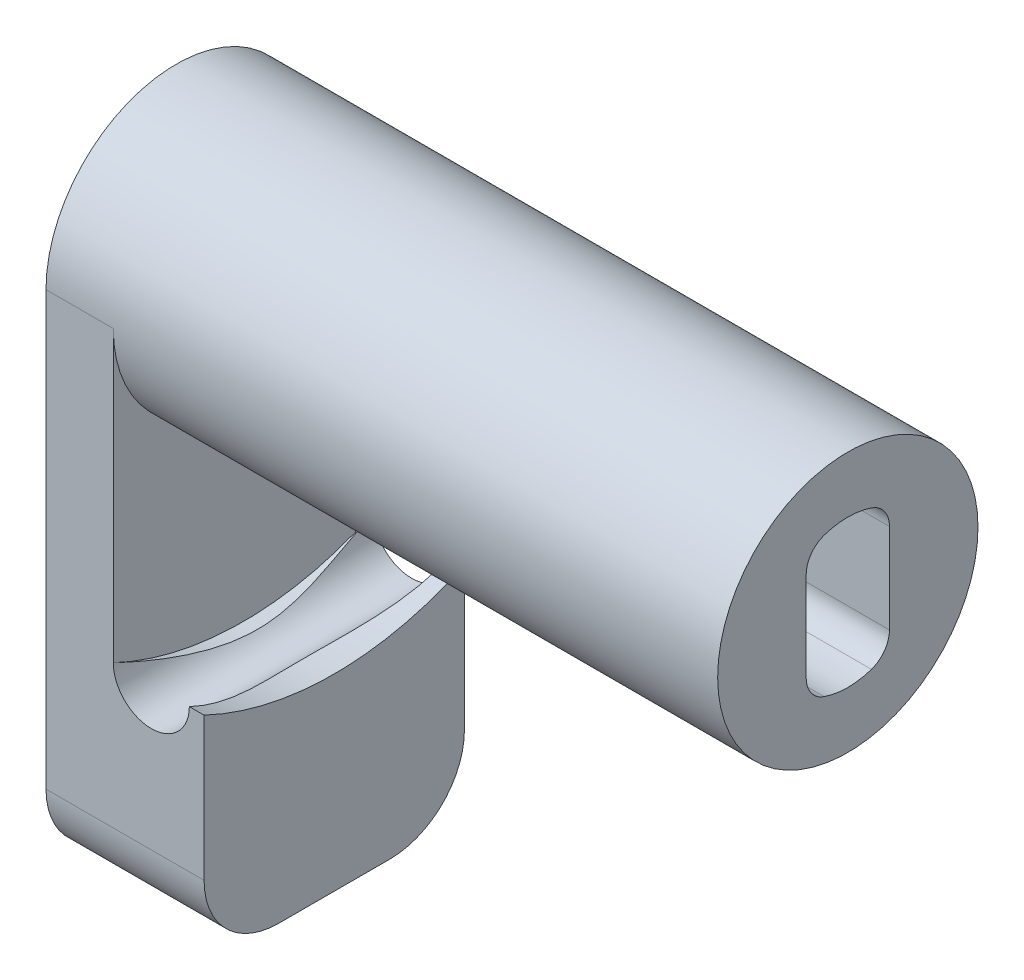
SolidWorks part; units mm, degrees
material "ABS"
ref_plane "Front Plane" through (0, 0, 0) normal (1, 0, 0) x (0, 1, 0)
ref_plane "Top Plane" through (0, 0, 0) normal (0, 0, 1) x (0, 1, 0)
ref_plane "Right Plane" through (0, 0, 0) normal (0, 1, 0) x (-1, 0, 0)
sketch "Sketch1" plane through (0, 0, 0) normal (1, 0, 0) x (0, 1, 0)
  circle A2 centre (0, 0) radius 8.7376
  dimension "D3" = 17.4752
extrude "Boss-Extrude1" add sketch "Sketch1" along normal blind 45.085 contours A2 region at (0, 0, 0)
sketch "Sketch10" plane through (0, 0, 0) normal (-1, 0, 0) x (0, -1, 0)
  line L0 (0, 8.7376) -> (34.036, 8.7376)
  line L2 (34.036, 8.7376) -> (34.036, -8.7376)
  line L3 (34.036, -8.7376) -> (0, -8.7376)
  circle A0 centre (0, 0) radius 8.7376 construction
  arc A2 (0, 8.7376) -> (0, -8.7376) centre (0, 0) cw
  dimension "D1" = 34.036
extrude "Boss-Extrude3" add sketch "Sketch10" against normal blind 4.516 contours L0 A2 L3 L2 region at (0, -20.3793, 0)
fillet "Fillet2" radius 5 2 edges at (2.258, -34.036, 8.7376) (2.258, -34.036, -8.7376)
sketch "Sketch14" [suppressed] plane through (0, 0, 0) normal (-1, 0, 0) x (0, 0, 1)
  line L0 (0.5115, -3.4237) -> (0.3944, -4.0089)
  line L1 (0, 0) -> (0, -4.064) construction
  line L2 (0, 0) -> (0.5606, -3.4335) construction
  line L3 (0.6039, -3.4087) -> (0.9011, -3.9262)
  line L4 (-0.6903, -3.3922) -> (-1.0005, -3.9021)
  line L5 (-0.5983, -3.4096) -> (-0.4961, -3.9976)
  line L6 (-1.8089, -2.9515) -> (-2.2748, -3.3245)
  line L7 (-1.7284, -2.9994) -> (-1.8334, -3.5869)
  line L8 (-2.7093, -2.1549) -> (-3.2746, -2.346)
  line L9 (-2.65, -2.2273) -> (-2.9496, -2.7435)
  line L10 (-3.2829, -1.0983) -> (-3.8795, -1.0846)
  line L11 (-3.252, -1.1867) -> (-3.7101, -1.5692)
  line L12 (-3.4605, 0.0907) -> (-4.0165, 0.3077)
  line L13 (-3.4617, -0.0029) -> (-4.023, -0.2057)
  line L14 (-3.2208, 1.2689) -> (-3.669, 1.6629)
  line L15 (-3.2539, 1.1813) -> (-3.8507, 1.1827)
  line L16 (-2.5926, 2.2939) -> (-2.879, 2.8175)
  line L17 (-2.6537, 2.223) -> (-3.214, 2.4284)
  line L18 (-1.6517, 3.0423) -> (-1.7417, 3.6323)
  line L19 (-1.7333, 2.9965) -> (-2.1896, 3.3812)
  line L20 (-0.5115, 3.4237) -> (-0.3944, 4.0089)
  line L21 (-0.6039, 3.4087) -> (-0.9011, 3.9262)
  line L22 (0.6903, 3.3922) -> (1.0005, 3.9021)
  line L23 (0.5983, 3.4096) -> (0.4961, 3.9976)
  line L24 (1.8089, 2.9515) -> (2.2748, 3.3245)
  line L25 (1.7284, 2.9994) -> (1.8334, 3.5869)
  line L26 (2.7093, 2.1549) -> (3.2746, 2.346)
  line L27 (2.65, 2.2273) -> (2.9496, 2.7435)
  line L28 (3.2829, 1.0983) -> (3.8795, 1.0846)
  line L29 (3.252, 1.1867) -> (3.7101, 1.5692)
  line L30 (3.4605, -0.0907) -> (4.0165, -0.3077)
  line L31 (3.4617, 0.0029) -> (4.023, 0.2057)
  line L32 (3.2208, -1.2689) -> (3.669, -1.6629)
  line L33 (3.2539, -1.1813) -> (3.8507, -1.1827)
  line L34 (2.5926, -2.2939) -> (2.879, -2.8175)
  line L35 (2.6537, -2.223) -> (3.214, -2.4284)
  line L36 (1.6517, -3.0423) -> (1.7417, -3.6323)
  line L37 (1.7333, -2.9965) -> (2.1896, -3.3812)
  line L38 (-0.1032, -4.0627) -> (0, -4.064)
  line L39 (-1.4865, -3.7824) -> (-1.39, -3.8189)
  line L40 (-2.6905, -3.0459) -> (-2.6123, -3.1132)
  line L41 (-3.5195, -2.032) -> (-3.57, -1.942)
  line L42 (-4.0023, -0.7057) -> (-4.0189, -0.6039)
  line L43 (-4.0023, 0.7057) -> (-3.9831, 0.8071)
  line L44 (-3.5195, 2.032) -> (-3.4668, 2.1207)
  line L45 (-2.6123, 3.1132) -> (-2.5324, 3.1785)
  line L46 (-1.39, 3.8189) -> (-1.2926, 3.853)
  line L47 (0, 4.064) -> (0.1032, 4.0627)
  line L48 (1.39, 3.8189) -> (1.4865, 3.7824)
  line L49 (2.6123, 3.1132) -> (2.6905, 3.0459)
  line L50 (3.5195, 2.032) -> (3.57, 1.942)
  line L51 (4.0023, 0.7057) -> (4.0189, 0.6039)
  line L52 (4.0023, -0.7057) -> (3.9831, -0.8071)
  line L53 (3.5195, -2.032) -> (3.4668, -2.1207)
  line L54 (2.6123, -3.1132) -> (2.5324, -3.1785)
  line L55 (1.39, -3.8189) -> (1.2926, -3.853)
  arc A0 (0.3497, -4.0489) -> (0, -4.064) centre (0, 0) cw
  arc A1 (0.3497, -4.0489) -> (0.3944, -4.0089) centre (0.3454, -3.9991) ccw
  arc A2 (0.5115, -3.4237) -> (0.6039, -3.4087) centre (0.5606, -3.4335) cw
  arc A3 (0.4203, -4.0631) -> (0.3944, -4.0089) centre (0.4434, -4.0187) cw
  arc A4 (0.4203, -4.0631) -> (0.7372, -4.2116) centre (2.3016, -0.4608) ccw
  arc A6 (0.9562, -3.9499) -> (0.9011, -3.9262) centre (0.9445, -3.9013) cw
  arc A7 (0.9562, -3.9499) -> (1.2926, -3.853) centre (0, 0) ccw
  arc A8 (-1.0562, -3.9243) -> (-1.39, -3.8189) centre (0, 0) cw
  arc A9 (-1.0562, -3.9243) -> (-1.0005, -3.9021) centre (-1.0432, -3.8761) ccw
  arc A10 (-0.6903, -3.3922) -> (-0.5983, -3.4096) centre (-0.6476, -3.4182) cw
  arc A11 (-0.4524, -4.0387) -> (-0.4961, -3.9976) centre (-0.4468, -3.9891) cw
  arc A12 (-0.4524, -4.0387) -> (-0.1032, -4.0627) centre (0, 0) ccw
  arc A13 (-2.3347, -3.3264) -> (-2.6123, -3.1132) centre (0, 0) cw
  arc A14 (-2.3347, -3.3264) -> (-2.2748, -3.3245) centre (-2.306, -3.2855) ccw
  arc A15 (-1.8089, -2.9515) -> (-1.7284, -2.9994) centre (-1.7776, -2.9906) cw
  arc A16 (-1.8064, -3.6405) -> (-1.8334, -3.5869) centre (-1.7842, -3.5957) cw
  arc A17 (-1.8064, -3.6405) -> (-1.4865, -3.7824) centre (0, 0) ccw
  arc A18 (-3.3316, -2.3273) -> (-3.5195, -2.032) centre (0, 0) cw
  arc A19 (-3.3316, -2.3273) -> (-3.2746, -2.346) centre (-3.2906, -2.2987) ccw
  arc A20 (-2.7093, -2.1549) -> (-2.65, -2.2273) centre (-2.6933, -2.2022) cw
  arc A21 (-2.9426, -2.8031) -> (-2.9496, -2.7435) centre (-2.9064, -2.7686) cw
  arc A22 (-2.9426, -2.8031) -> (-2.6905, -3.0459) centre (0, 0) ccw
  arc A23 (-3.9267, -1.0475) -> (-4.0023, -0.7057) centre (0, 0) cw
  arc A24 (-3.9267, -1.0475) -> (-3.8795, -1.0846) centre (-3.8784, -1.0346) ccw
  arc A25 (-3.2829, -1.0983) -> (-3.252, -1.1867) centre (-3.284, -1.1483) cw
  arc A26 (-3.7238, -1.6276) -> (-3.7101, -1.5692) centre (-3.678, -1.6076) cw
  arc A27 (-3.7238, -1.6276) -> (-3.57, -1.942) centre (0, 0) ccw
  arc A28 (-4.0481, 0.3587) -> (-4.0023, 0.7057) centre (0, 0) cw
  arc A29 (-4.0481, 0.3587) -> (-4.0165, 0.3077) centre (-3.9983, 0.3543) ccw
  arc A30 (-3.4605, 0.0907) -> (-3.4617, -0.0029) centre (-3.4787, 0.0442) cw
  arc A31 (-4.0559, -0.2558) -> (-4.023, -0.2057) centre (-4.006, -0.2527) cw
  arc A32 (-4.0559, -0.2558) -> (-4.0189, -0.6039) centre (0, 0) ccw
  arc A33 (-3.6813, 1.7216) -> (-3.5195, 2.032) centre (0, 0) cw
  arc A34 (-3.6813, 1.7216) -> (-3.669, 1.6629) centre (-3.636, 1.7005) ccw
  arc A35 (-3.2208, 1.2689) -> (-3.2539, 1.1813) centre (-3.2538, 1.2313) cw
  arc A36 (-3.8988, 1.1468) -> (-3.8507, 1.1827) centre (-3.8509, 1.1327) cw
  arc A37 (-3.8988, 1.1468) -> (-3.9831, 0.8071) centre (0, 0) ccw
  arc A38 (-2.8705, 2.8769) -> (-2.6123, 3.1132) centre (0, 0) cw
  arc A39 (-2.8705, 2.8769) -> (-2.879, 2.8175) centre (-2.8352, 2.8415) ccw
  arc A40 (-2.5926, 2.2939) -> (-2.6537, 2.223) centre (-2.6365, 2.2699) cw
  arc A41 (-3.2715, 2.4111) -> (-3.214, 2.4284) centre (-3.2312, 2.3815) cw
  arc A42 (-3.2715, 2.4111) -> (-3.4668, 2.1207) centre (0, 0) ccw
  arc A43 (-1.7134, 3.6852) -> (-1.39, 3.8189) centre (0, 0) cw
  arc A44 (-1.7134, 3.6852) -> (-1.7417, 3.6323) centre (-1.6923, 3.6398) ccw
  arc A45 (-1.6517, 3.0423) -> (-1.7333, 2.9965) centre (-1.7011, 3.0348) cw
  arc A46 (-2.2495, 3.3846) -> (-2.1896, 3.3812) centre (-2.2218, 3.343) cw
  arc A47 (-2.2495, 3.3846) -> (-2.5324, 3.1785) centre (0, 0) ccw
  arc A48 (-0.3497, 4.0489) -> (0, 4.064) centre (0, 0) cw
  arc A49 (-0.3497, 4.0489) -> (-0.3944, 4.0089) centre (-0.3454, 3.9991) ccw
  arc A50 (-0.5115, 3.4237) -> (-0.6039, 3.4087) centre (-0.5606, 3.4335) cw
  arc A51 (-0.9562, 3.9499) -> (-0.9011, 3.9262) centre (-0.9445, 3.9013) cw
  arc A52 (-0.9562, 3.9499) -> (-1.2926, 3.853) centre (0, 0) ccw
  arc A53 (1.0562, 3.9243) -> (1.39, 3.8189) centre (0, 0) cw
  arc A54 (1.0562, 3.9243) -> (1.0005, 3.9021) centre (1.0432, 3.8761) ccw
  arc A55 (0.6903, 3.3922) -> (0.5983, 3.4096) centre (0.6476, 3.4182) cw
  arc A56 (0.4524, 4.0387) -> (0.4961, 3.9976) centre (0.4468, 3.9891) cw
  arc A57 (0.4524, 4.0387) -> (0.1032, 4.0627) centre (0, 0) ccw
  arc A58 (2.3347, 3.3264) -> (2.6123, 3.1132) centre (0, 0) cw
  arc A59 (2.3347, 3.3264) -> (2.2748, 3.3245) centre (2.306, 3.2855) ccw
  arc A60 (1.8089, 2.9515) -> (1.7284, 2.9994) centre (1.7776, 2.9906) cw
  arc A61 (1.8064, 3.6405) -> (1.8334, 3.5869) centre (1.7842, 3.5957) cw
  arc A62 (1.8064, 3.6405) -> (1.4865, 3.7824) centre (0, 0) ccw
  arc A63 (3.3316, 2.3273) -> (3.5195, 2.032) centre (0, 0) cw
  arc A64 (3.3316, 2.3273) -> (3.2746, 2.346) centre (3.2906, 2.2987) ccw
  arc A65 (2.7093, 2.1549) -> (2.65, 2.2273) centre (2.6933, 2.2022) cw
  arc A66 (2.9426, 2.8031) -> (2.9496, 2.7435) centre (2.9064, 2.7686) cw
  arc A67 (2.9426, 2.8031) -> (2.6905, 3.0459) centre (0, 0) ccw
  arc A68 (3.9267, 1.0475) -> (4.0023, 0.7057) centre (0, 0) cw
  arc A69 (3.9267, 1.0475) -> (3.8795, 1.0846) centre (3.8784, 1.0346) ccw
  arc A70 (3.2829, 1.0983) -> (3.252, 1.1867) centre (3.284, 1.1483) cw
  arc A71 (3.7238, 1.6276) -> (3.7101, 1.5692) centre (3.678, 1.6076) cw
  arc A72 (3.7238, 1.6276) -> (3.57, 1.942) centre (0, 0) ccw
  arc A73 (4.0481, -0.3587) -> (4.0023, -0.7057) centre (0, 0) cw
  arc A74 (4.0481, -0.3587) -> (4.0165, -0.3077) centre (3.9983, -0.3543) ccw
  arc A75 (3.4605, -0.0907) -> (3.4617, 0.0029) centre (3.4787, -0.0442) cw
  arc A76 (4.0559, 0.2558) -> (4.023, 0.2057) centre (4.006, 0.2527) cw
  arc A77 (4.0559, 0.2558) -> (4.0189, 0.6039) centre (0, 0) ccw
  arc A78 (3.6813, -1.7216) -> (3.5195, -2.032) centre (0, 0) cw
  arc A79 (3.6813, -1.7216) -> (3.669, -1.6629) centre (3.636, -1.7005) ccw
  arc A80 (3.2208, -1.2689) -> (3.2539, -1.1813) centre (3.2538, -1.2313) cw
  arc A81 (3.8988, -1.1468) -> (3.8507, -1.1827) centre (3.8509, -1.1327) cw
  arc A82 (3.8988, -1.1468) -> (3.9831, -0.8071) centre (0, 0) ccw
  arc A83 (2.8705, -2.8769) -> (2.6123, -3.1132) centre (0, 0) cw
  arc A84 (2.8705, -2.8769) -> (2.879, -2.8175) centre (2.8352, -2.8415) ccw
  arc A85 (2.5926, -2.2939) -> (2.6537, -2.223) centre (2.6365, -2.2699) cw
  arc A86 (3.2715, -2.4111) -> (3.214, -2.4284) centre (3.2312, -2.3815) cw
  arc A87 (3.2715, -2.4111) -> (3.4668, -2.1207) centre (0, 0) ccw
  arc A88 (1.7134, -3.6852) -> (1.39, -3.8189) centre (0, 0) cw
  arc A89 (1.7134, -3.6852) -> (1.7417, -3.6323) centre (1.6923, -3.6398) ccw
  arc A90 (1.6517, -3.0423) -> (1.7333, -2.9965) centre (1.7011, -3.0348) cw
  arc A91 (2.2495, -3.3846) -> (2.1896, -3.3812) centre (2.2218, -3.343) cw
  arc A92 (2.2495, -3.3846) -> (2.5324, -3.1785) centre (0, 0) ccw
  point P207 (0, 0)
  dimension "D1" = 4.064
  dimension "D2" = 0.05
  dimension "D3" = 0.05
  dimension "D4" = 0.04
  dimension "D5" = 18
  dimension "D6" = 0.5968
  dimension "D8" = 0.35
sketch "Sketch15" plane through (4.516, 0, 0) normal (1, 0, 0) x (0, 1, 0)
  line L1 (-29.036, 8.7376) -> (-18.796, 8.7376)
  line L2 (-18.796, 8.7376) -> (-18.796, -8.7376)
  line L3 (0, 8.7376) -> (-29.036, 8.7376) construction
  line L4 (-29.036, -8.7376) -> (-18.796, -8.7376)
  line L5 (-34.036, 3.7376) -> (-34.036, -3.7376) construction
  line L6 (-34.036, 3.7376) -> (-34.036, -3.7376)
  line L8 (-29.036, -8.7376) -> (0, -8.7376) construction
  line L13 (0, 8.7376) -> (-29.036, 8.7376)
  line L14 (-34.036, 3.7376) -> (-34.036, -3.7376)
  line L15 (-29.036, -8.7376) -> (0, -8.7376)
  line L17 (-34.036, 3.7376) -> (-34.036, -3.7376)
  arc A0 (-29.036, 8.7376) -> (-34.036, 3.7376) centre (-29.036, 3.7376) ccw construction
  arc A1 (-34.036, -3.7376) -> (-29.036, -8.7376) centre (-29.036, -3.7376) ccw construction
  arc A2 (-29.036, 8.7376) -> (-34.036, 3.7376) centre (-29.036, 3.7376) ccw
  arc A3 (-34.036, -3.7376) -> (-29.036, -8.7376) centre (-29.036, -3.7376) ccw
  arc A7 (-29.036, 8.7376) -> (-34.036, 3.7376) centre (-29.036, 3.7376) ccw
  arc A8 (-34.036, -3.7376) -> (-29.036, -8.7376) centre (-29.036, -3.7376) ccw
  arc A9 (0, 8.7376) -> (0, -8.7376) centre (0, 0) ccw
  arc A10 (-29.036, 8.7376) -> (-34.036, 3.7376) centre (-29.036, 3.7376) ccw
  arc A11 (-34.036, -3.7376) -> (-29.036, -8.7376) centre (-29.036, -3.7376) ccw
  arc A12 (0, 8.7376) -> (0, -8.7376) centre (0, 0) ccw
  line M2 (0, 8.7376) -> (-29.036, 8.7376)
  arc M3 (-29.036, 8.7376) -> (-34.036, 3.7376) centre (-29.036, 3.7376) ccw
  line M4 (-34.036, 3.7376) -> (-34.036, -3.7376)
  arc M5 (-34.036, -3.7376) -> (-29.036, -8.7376) centre (-29.036, -3.7376) ccw
  dimension "D1" = 15.24
  dimension "D2" = 0
extrude "Boss-Extrude4" add sketch "Sketch15" along normal blind 6.096 contours M2 M3 M4 M5 region at (4.516, -26.143, 0)
sketch "Sketch21" plane through (10.612, 0, 0) normal (1, 0, 0) x (0, 1, 0)
  line L2 (-18.796, -8.7376) -> (-18.796, 8.7376)
  line L4 (-29.036, 8.7376) -> (-18.796, 8.7376) construction
  line L5 (-19.431, -8.7376) -> (-18.796, -8.7376)
  line L6 (-18.796, 8.7376) -> (-18.796, -8.7376) construction
  line L8 (-18.796, -8.7376) -> (0, -8.7376) construction
  line L14 (-18.796, -8.7376) -> (-18.796, 8.7376) construction
  line L20 (-18.796, 8.7376) -> (-29.036, 8.7376)
  arc A2 (-19.431, -8.7376) -> (-19.431, 8.7376) centre (-1.0855, 0) cw
  dimension "D4" = 20.32
  dimension "D2" = 0.635
  dimension "D3" = 0.635
extrude "Cut-Extrude8" cut sketch "Sketch21" against normal up to surface (6.096 mm away) contours A2 L2 region at (10.612, -19.8652, 0) up to face at (4.516, -11.5824, 0)
sketch "Sketch22" plane through (45.085, 0, 0) normal (1, 0, 0) x (0, 1, 0)
  line L7 (-4.0897, -2.794) -> (4.0897, 2.794) construction
  line L8 (-4.0897, 2.794) -> (4.0897, -2.794) construction
  line L11 (-4.0897, -2.794) -> (4.0897, -2.794)
  line L13 (-4.0897, 2.794) -> (4.0897, 2.794)
  line L15 (-4.0897, -2.794) -> (4.0897, 2.794) construction
  line L16 (-4.0897, 2.794) -> (4.0897, -2.794) construction
  arc A3 (-4.0897, 2.794) -> (-4.0897, -2.794) centre (0, 0) ccw
  arc A4 (4.0897, -2.794) -> (4.0897, 2.794) centre (0, 0) ccw
  dimension "D2" = 9.906
  dimension "D3" = 5.588
extrude "Cut-Extrude10" cut sketch "Sketch22" against normal blind 12.192
fillet "Fillet11" radius 1.778 4 edges at (38.989, 4.0897, -2.794) (38.989, 4.0897, 2.794) (38.989, -4.0897, -2.794) (38.989, -4.0897, 2.794)
sketch "Sketch25" plane through (0, 0, -8.7376) normal (0, 0, -1) x (1, 0, 0)
  line L3 (4.516, 19.431) -> (4.516, 0) construction
  line L4 (4.516, 19.431) -> (10.612, 19.431) construction
  circle A0 centre (7.0687, 19.431) radius 2.5527
  dimension "D1" = 5.1054
extrude "Cut-Extrude14" cut sketch "Sketch25" against normal through all
sketch "Sketch26" plane through (0, 0, 0) normal (-1, 0, 0) x (0, -1, 0)
  line L1 (3.6846, 1.7145) -> (7.1771, 1.7145)
  line L2 (3.6846, 1.7145) -> (3.6846, -1.7145) construction
  line L3 (3.6846, -1.7145) -> (7.1771, -1.7145)
  line L4 (7.1771, 1.7145) -> (7.1771, -1.7145)
  arc A0 (3.6846, 1.7145) -> (3.6846, -1.7145) centre (0, 0) ccw
  dimension "D1" = 8.128
  dimension "D2" = 3.429
  dimension "D3" = 3.4925
extrude "Cut-Extrude15" cut sketch "Sketch26" against normal blind 21.59
fillet "Fillet12" radius 1.5875 4 edges at (10.795, -3.6846, 1.7145) (10.795, -7.1771, 1.7145) (10.795, -3.6846, -1.7145) (10.795, -7.1771, -1.7145)
